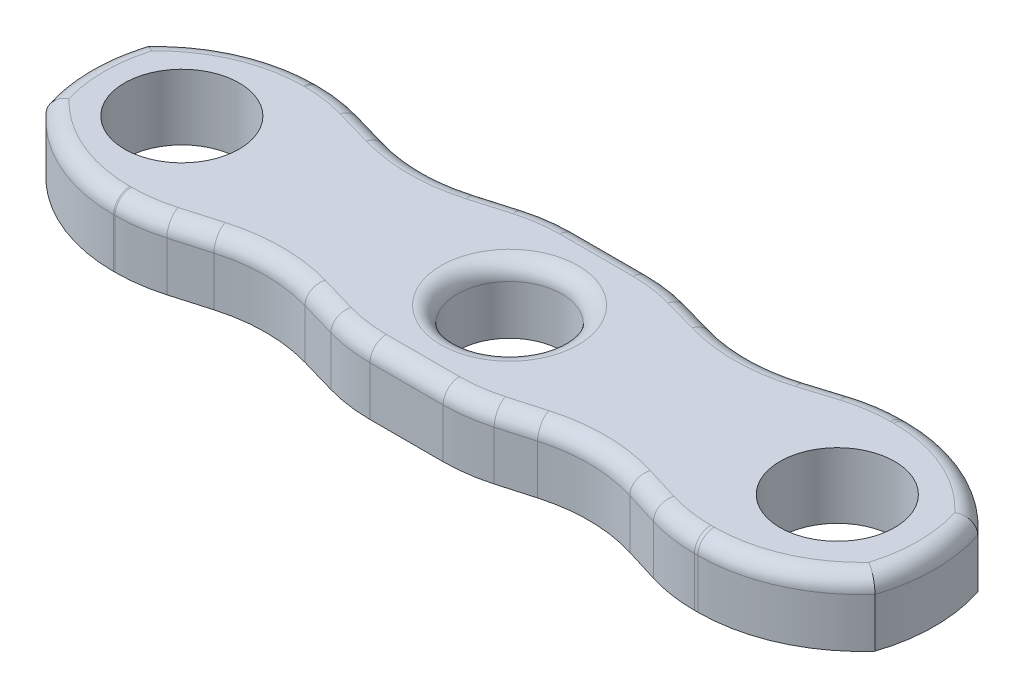
SolidWorks part; units mm, degrees
ref_plane "Front Plane" through (0, 0, 0) normal (0, 0, 1) x (1, 0, 0)
ref_plane "Top Plane" through (0, 0, 0) normal (0, 1, 0) x (1, 0, 0)
ref_plane "Right Plane" through (0, 0, 0) normal (1, 0, 0) x (0, 0, -1)
sketch "Sketch2" plane through (0, 0, 0) normal (0, 1, 0) x (1, 0, 0)
  line L0 (-25.2035, 0) -> (20.3303, 0) construction
  line L1 (-10.3906, 4) -> (-15.0094, 4)
  line L2 (-15.0094, 4) -> (-17.3189, 0)
  line L3 (-17.3189, 0) -> (-15.0094, -4)
  line L4 (-15.0094, -4) -> (-10.3906, -4)
  line L5 (-10.3906, -4) -> (-8.0811, 0)
  line L6 (-8.0811, 0) -> (-10.3906, 4)
  line L7 (-2.3094, 4) -> (-4.6189, 0)
  line L8 (-4.6189, 0) -> (-2.3094, -4)
  line L9 (-2.3094, -4) -> (2.3094, -4)
  line L10 (2.3094, -4) -> (4.6189, 0)
  line L11 (4.6189, 0) -> (2.3094, 4)
  line L12 (2.3094, 4) -> (-2.3094, 4)
  line L13 (10.3235, 4.1163) -> (7.9469, 0)
  line L14 (7.9469, 0) -> (10.3235, -4.1163)
  line L15 (10.3235, -4.1163) -> (15.0765, -4.1163)
  line L16 (15.0765, -4.1163) -> (17.4531, 0)
  line L17 (17.4531, 0) -> (15.0765, 4.1163)
  line L18 (15.0765, 4.1163) -> (10.3235, 4.1163)
  line L23 (-10.3906, -4) -> (-6.35, -2.8333)
  line L24 (-3.4641, -2) -> (-2.3094, -4)
  line L25 (-2.3094, -4) -> (-6.35, -2.8333)
  line L26 (-9.2359, -2) -> (-10.3906, -4)
  line L27 (-10.3906, 4) -> (-6.35, 2.8333)
  line L28 (-3.4641, 2) -> (-2.3094, 4)
  line L29 (-6.35, 2.8333) -> (-2.3094, 4)
  line L30 (-9.4504, 2.3716) -> (-10.3906, 4)
  line L31 (2.3094, 4) -> (6.2828, 2.8696)
  line L32 (9.1352, 2.0581) -> (10.3235, 4.1163)
  line L33 (10.3235, 4.1163) -> (6.2828, 2.8696)
  line L34 (3.4641, 2) -> (2.3094, 4)
  line L35 (2.3094, 4) -> (3.4641, 2)
  line L36 (2.4255, -4) -> (2.3094, -4)
  line L37 (2.3094, -4) -> (6.2828, -2.8696)
  line L38 (9.1352, -2.0581) -> (10.3235, -4.1163)
  line L39 (10.3235, -4.1163) -> (6.2828, -2.8696)
  line L40 (3.4641, -2) -> (2.3094, -4)
  circle A0 centre (0, 0) radius 2.025
  circle A1 centre (-12.7, 0) radius 2.2225
  circle A2 centre (12.7, 0) radius 2.2225
  circle A5 centre (12.7, 0) radius 2.2225
  dimension "D1" = 4.445
  dimension "D4" = 4.05
  dimension "D5" = 4.445
  dimension "D2" = 12.7
  dimension "D3" = 12.7
  dimension "D6" = 120
  dimension "D7" = 0
  dimension "D8" = 0
  dimension "D9" = 0
  dimension "D10" = 60
  dimension "D11" = 60
extrude "Boss-Extrude3" add sketch "Sketch2" along normal blind 2.54 contours L2 L0 A1 L6 L1 | L0 L3 L4 L5 A1 | L6 L0 L7 L29 L27 | L0 L5 L23 L25 L8 | L7 L0 A0 L11 L12 | L0 L8 L9 L10 A0 | L11 L0 L13 L33 L31 | L0 L10 L37 L39 L14 | L13 L0 A2 L17 L18 | L0 L14 L15 L16 A5 region at (-12.7, 0, -2.3232) region at (-9.2793, 0, 0.1007) region at (-6.35, 0, -1.9218) region at (-6.35, 0, 1.9218) region at (0, 0, -2.0559) region at (0, 0, 2.0559) region at (6.3112, 0, -1.9556) region at (6.3112, 0, 1.9556) region at (8.6308, 0, -0.9773) region at (9.2122, 0, 0.1036)
fillet "Fillet1" radius 6.35 18 edges at (-10.3906, 1.27, -4) (-6.35, 1.27, -2.8333) (-2.3094, 1.27, -4) (2.3094, 1.27, -4) (6.2828, 1.27, -2.8696) (10.3235, 1.27, -4.1163) (15.0765, 1.27, -4.1163) (17.4531, 1.27, 0) (15.0765, 1.27, 4.1163) (10.3235, 1.27, 4.1163) (6.2828, 1.27, 2.8696) (2.3094, 1.27, 4) (-2.3094, 1.27, 4) (-6.35, 1.27, 2.8333) (-10.3906, 1.27, 4) (-15.0094, 1.27, 4) (-17.3189, 1.27, 0) (-15.0094, 1.27, -4)
fillet "Fillet2" radius 0.635 33 edges at (0, 2.54, 2.025) (-6.35, 2.54, -3.0927) (-3.8805, 2.54, -3.5464) (-2.3006, 2.54, -3.9374) (0.0064, 2.54, -4) (2.3009, 2.54, -3.9392) (3.8167, 2.54, -3.5712) (6.2798, 2.54, -3.1428) (8.7452, 2.54, -3.6294) (10.3342, 2.54, -4.0453) (11.3456, 2.54, -4.1163) (14.0074, 2.54, -3.5609) (16.4707, 2.54, 0) (14.0074, 2.54, 3.5609) (11.3456, 2.54, 4.1163) (10.3342, 2.54, 4.0453) (8.7452, 2.54, 3.6294) (6.2798, 2.54, 3.1428) (3.8167, 2.54, 3.5712) (2.3009, 2.54, 3.9392) (0.0064, 2.54, 4) (-2.3006, 2.54, 3.9374) (-3.8805, 2.54, 3.5464) (-6.35, 2.54, 3.0927) (-8.8195, 2.54, 3.5464) (-10.3994, 2.54, 3.9374) (-11.3161, 2.54, 4) (-13.909, 2.54, 3.4586) (-16.3365, 2.54, 0) (-13.909, 2.54, -3.4586) (-11.3161, 2.54, -4) (-10.3994, 2.54, -3.9374) (-8.8195, 2.54, -3.5464)
